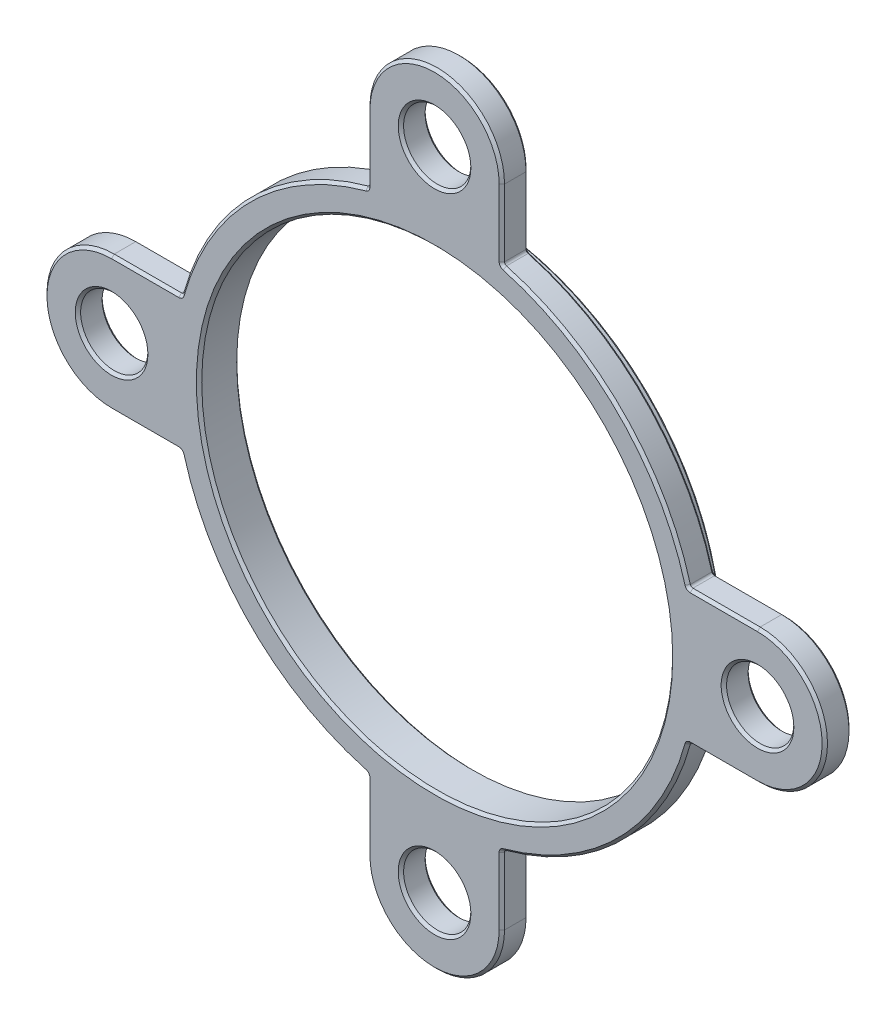
SolidWorks part; units mm, degrees
ref_plane "Спереди" through (0, 0, 0) normal (0, 0, 1) x (1, 0, 0)
ref_plane "Сверху" through (0, 0, 0) normal (0, 1, 0) x (1, 0, 0)
ref_plane "Справа" through (0, 0, 0) normal (1, 0, 0) x (0, 0, -1)
sketch "Эскиз1" plane through (0, 0, 0) normal (0, 0, 1) x (1, 0, 0)
  line L0 (0, 0) -> (0, 50000) construction
  line L1 (5, -24) -> (5, -18.8481)
  line L2 (-5, -24) -> (-5, -18.8481)
  line L3 (-24, -5) -> (-18.8481, -5)
  line L4 (-24, 5) -> (-18.8481, 5)
  line L5 (-5, 24) -> (-5, 18.8481)
  line L6 (5, 24) -> (5, 18.8481)
  line L7 (24, 5) -> (18.8481, 5)
  line L8 (24, -5) -> (18.8481, -5)
  arc A0 (5, -18.8481) -> (18.8481, -5) centre (0, 0) ccw
  circle A2 centre (0, -24) radius 2.5
  arc A3 (-5, -24) -> (5, -24) centre (0, -24) ccw
  circle A4 centre (-24, 0) radius 2.5
  arc A5 (-24, 5) -> (-24, -5) centre (-24, 0) ccw
  circle A6 centre (0, 24) radius 2.5
  arc A7 (5, 24) -> (-5, 24) centre (0, 24) ccw
  circle A8 centre (24, 0) radius 2.5
  arc A9 (24, -5) -> (24, 5) centre (24, 0) ccw
  arc A10 (-5, 18.8481) -> (-18.8481, 5) centre (0, 0) ccw
  arc A11 (-18.8481, -5) -> (-5, -18.8481) centre (0, 0) ccw
  arc A12 (18.8481, 5) -> (5, 18.8481) centre (0, 0) ccw
  circle A13 centre (0, 0) radius 17.5
  point P31 (0, 0)
  dimension "D1" = 39
  dimension "D2" = 24
  dimension "D3" = 5
  dimension "D4" = 10
  dimension "D6" = 35
  dimension "D5" = 4
extrude "Бобышка-Вытянуть1" add sketch "Эскиз1" along normal blind 2
sketch "Эскиз2" plane through (0, 0, 0) normal (0, 0, -1) x (-1, 0, 0)
  circle A0 centre (0, 0) radius 17.5
  circle A1 centre (0, 0) radius 18.5
  dimension "D1" = 37
  dimension "D2" = 35
extrude "Бобышка-Вытянуть2" add sketch "Эскиз2" along normal blind 1
fillet "Скругление1" radius 0.2 9 edges at (18.5, 0, 0) (18.8481, 5, 1) (5, 18.8481, 1) (-5, 18.8481, 1) (-18.8481, 5, 1) (-18.8481, -5, 1) (-5, -18.8481, 1) (5, -18.8481, 1) (18.8481, -5, 1)
chamfer "Фаска1" distance 0.2 angle 45 59 edges at (5, -21.5007, 0) (13.7886, -13.7886, 0) (21.5007, -5, 0) (29, 0, 0) (21.5007, 5, 0) (13.7886, 13.7886, 0) (5, 21.5007, 0) (0, 29, 0) (-5, 21.5007, 0) (-13.7886, 13.7886, 0) (-21.5007, 5, 0) (-29, 0, 0) (-21.5007, -5, 0) (-13.7886, -13.7886, 0) (-5, -21.5007, 0) (0, -29, 0) (2.5, -24, 0) (-21.5, 0, 0) (2.5, 24, 0) (26.5, 0, 0) (-17.5, 0, -1) (-18.5, 0, -1) (26.5, 0, 2) (-21.5, 0, 2) (17.5, 0, 2) (-5, -21.5007, 2) (-13.7886, -13.7886, 2) (-21.5007, -5, 2) (-29, 0, 2) (-21.5007, 5, 2) (-13.7886, 13.7886, 2) (-5, 21.5007, 2) (0, 29, 2) (5, 21.5007, 2) (13.7886, 13.7886, 2) (21.5007, 5, 2) (29, 0, 2) (21.5007, -5, 2) (13.7886, -13.7886, 2) (5, -21.5007, 2) (0, -29, 2) (2.5, -24, 2) (2.5, 24, 2) (5.041, -18.88, 0) (18.88, -5.041, 0) (18.88, 5.041, 0) (5.041, 18.88, 0) (-5.041, 18.88, 0) (-18.88, 5.041, 0) (-18.88, -5.041, 0) (-5.041, -18.88, 0) (-5.041, -18.88, 2) (-18.88, -5.041, 2) (-18.88, 5.041, 2) (-5.041, 18.88, 2) (5.041, 18.88, 2) (18.88, 5.041, 2) (18.88, -5.041, 2) (5.041, -18.88, 2)
